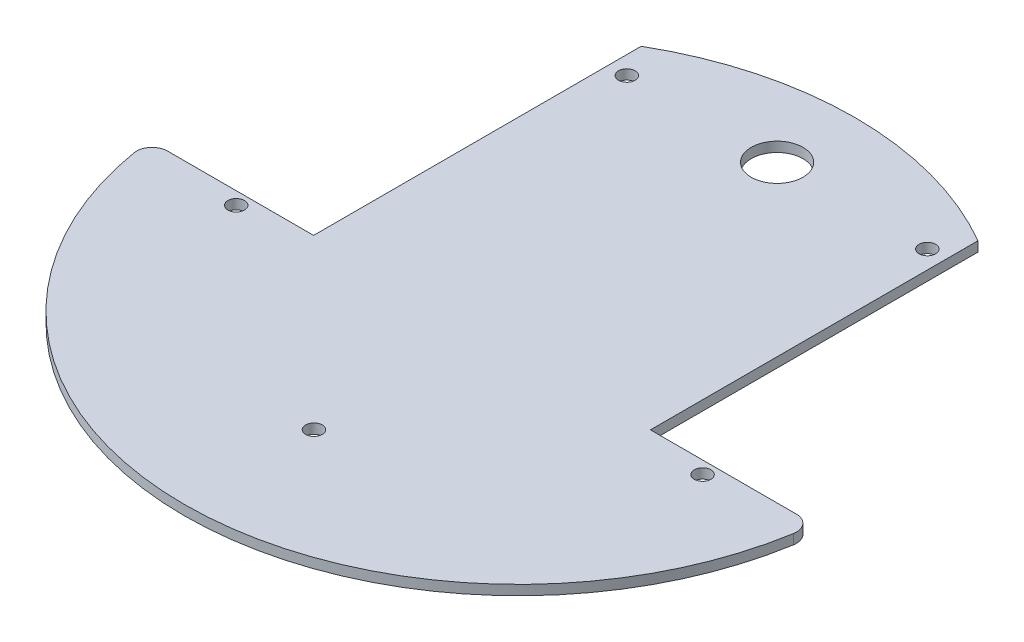
SolidWorks part; units mm, degrees
material "ABS"
ref_plane "Front Plane" through (0, 0, 0) normal (0, 0, 1) x (1, 0, 0)
ref_plane "Top Plane" through (0, 0, 0) normal (0, 1, 0) x (1, 0, 0)
ref_plane "Right Plane" through (0, 0, 0) normal (1, 0, 0) x (0, 0, -1)
sketch "Sketch1" plane through (0, 0, 0) normal (0, 1, 0) x (1, 0, 0)
  line L1 (-18, -10) -> (18, -10)
  line L2 (-18, -10) -> (-18, 10)
  line L3 (-18, 10) -> (18, 10)
  line L4 (18, -10) -> (18, 10)
  line L5 (-18, -10) -> (18, 10) construction
  line L6 (-18, 10) -> (18, -10) construction
  point P0 (0, 0)
  dimension "D1" = 36
  dimension "D2" = 20
extrude "Boss-Extrude1" add sketch "Sketch1" along normal blind 1.9
sketch "Sketch3" plane through (0, 0, 0) normal (0, -1, 0) x (1, 0, 0)
  line L0 (0, 0) -> (0, 52.1486) construction
  line L1 (37.5, -26.8695) -> (-37.5, -26.8695) construction
  line L2 (37.5, -26.8695) -> (32.5, -26.8695)
  line L3 (0, 0) -> (0, -36.2287) construction
  line L4 (-37.5, -26.8695) -> (-32.5, -26.8695)
  line L5 (32.5, -26.8695) -> (32.5, 33.1305)
  line L6 (-32.5, -26.8695) -> (-32.5, 33.1305)
  line L7 (32.5, 33.1305) -> (60.6723, 33.1305)
  line L9 (-32.5, 33.1305) -> (-60.6723, 33.1305)
  arc A0 (37.5, -26.8695) -> (-37.5, -26.8695) centre (0, 26.0743) cw
  arc A1 (71.1641, 14.6803) -> (48.1446, 79.705) centre (0, 26.0743) ccw construction
  arc A2 (68.1909, 19.5743) -> (51.8431, 70.8464) centre (0, 26.0743) ccw construction
  arc A3 (63.6319, 36.621) -> (-63.6319, 36.621) centre (0, 26.0743) ccw
  circle A4 centre (0, 26.0743) radius 72.5 construction
  arc A5 (-60.6723, 33.1305) -> (-63.6319, 36.621) centre (-60.6723, 36.1305) cw
  arc A6 (60.6723, 33.1305) -> (63.6319, 36.621) centre (60.6723, 36.1305) ccw
  point P7 (0, 26.0743)
  point P20 (-64.1129, 33.1305)
  point P26 (64.1129, 33.1305)
  dimension "D1" = 4
  dimension "D3" = 5
  dimension "D4" = 60
  dimension "D5" = 3
  dimension "D6" = 7.0562
  dimension "D2" = 65
extrude "Boss-Extrude2" add sketch "Sketch3" against normal blind 1.9
sketch "Sketch4" plane through (0, 1.9, 0) normal (0, 1, 0) x (1, 0, 0)
  line L0 (-32.5, 26.8695) -> (-32.5, 34.1947)
  line L1 (-32.5, 34.1947) -> (-40.4421, 34.1947)
  line L2 (-40.4421, 34.1947) -> (-37.5, 26.8695)
  line L3 (-37.5, 26.8695) -> (-32.5, 26.8695)
  line L4 (0, 0) -> (0, 49.3906) construction
  line L5 (37.5, 26.8695) -> (32.5, 26.8695)
  line L6 (40.4421, 34.1947) -> (37.5, 26.8695)
  line L7 (32.5, 34.1947) -> (40.4421, 34.1947)
  line L8 (32.5, 26.8695) -> (32.5, 34.1947)
  arc A0 (37.5, 26.8695) -> (-37.5, 26.8695) centre (0, -26.0743) ccw construction
extrude "Cut-Extrude1" cut sketch "Sketch4" against normal blind 10
sketch "Sketch5" plane through (0, 1.9, 0) normal (0, 1, 0) x (1, 0, 0)
  line L0 (0, 0) -> (0, 38.8048) construction
  circle A0 centre (0, 23.8048) radius 5
  arc A1 (32.5, 30.0777) -> (-32.5, 30.0777) centre (0, -26.0743) ccw construction
  dimension "D1" = 10
  dimension "D2" = 15
extrude "Cut-Extrude2" cut sketch "Sketch5" against normal up to surface (1.9 mm away) up to face at (0, 0, 23.683)
sketch "Sketch6" plane through (0, 1.9, 0) normal (0, 1, 0) x (1, 0, 0)
  line L0 (0, 38.8048) -> (0, -90.5743) construction
  line L1 (-45, -35.5743) -> (45, -35.5743) construction
  line L2 (-29, 23.8048) -> (29, 23.8048) construction
  line L3 (-45, -31.5743) -> (-45, -49.6893) construction
  line L4 (-50, -31.5743) -> (-40, -31.5743) construction
  arc A0 (32.5, 30.0777) -> (-32.5, 30.0777) centre (0, -26.0743) ccw construction
  arc A1 (-63.6319, -36.621) -> (63.6319, -36.621) centre (0, -26.0743) ccw construction
  circle A2 centre (0, -65.5743) radius 1.6
  circle A3 centre (-45, -35.5743) radius 1.6
  circle A4 centre (45, -35.5743) radius 1.6
  circle A5 centre (-29, 23.8048) radius 1.6
  circle A6 centre (29, 23.8048) radius 1.6
  dimension "D1" = 25
  dimension "D2" = 3.2
  dimension "D3" = 4
  dimension "D5" = 58
extrude "Cut-Extrude3" cut sketch "Sketch6" against normal up to surface (1.9 mm away) up to face at (0, 0, -28.8048)
